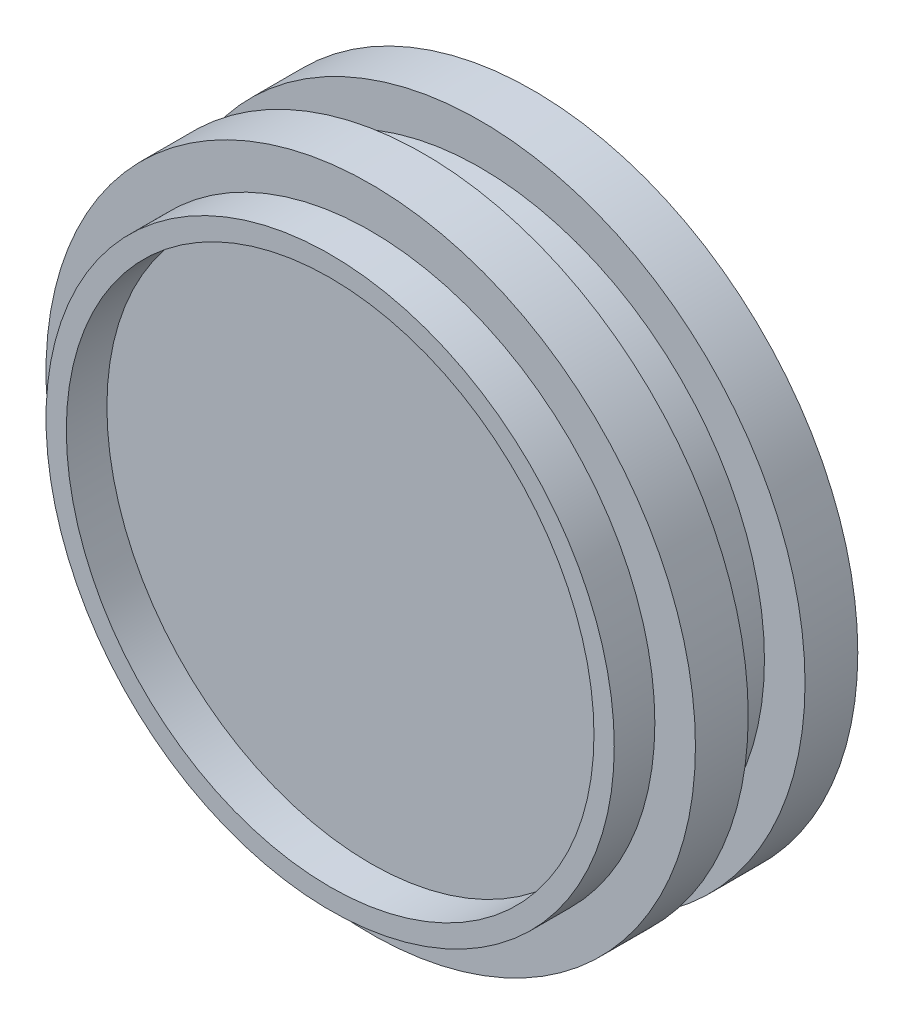
SolidWorks part; units mm, degrees
ref_plane "Front Plane" through (0, 0, 0) normal (0, 0, 1) x (1, 0, 0)
ref_plane "Top Plane" through (0, 0, 0) normal (0, 1, 0) x (1, 0, 0)
ref_plane "Right Plane" through (0, 0, 0) normal (1, 0, 0) x (0, 0, -1)
sketch "Sketch1" plane through (0, 0, 0) normal (0, 0, 1) x (1, 0, 0)
  circle A0 centre (0, 0) radius 82.55
  circle A1 centre (0, 0) radius 88.9
  circle A2 centre (0, 0) radius 101.6
  dimension "D1" = 165.1
  dimension "D2" = 177.8
  dimension "D3" = 203.2
extrude "Boss-Extrude1" add sketch "Sketch1" along normal blind 12.7 and the other way blind 50.8 contours A1 A0 region at (-86.3855, 0, 0)
extrude "Boss-Extrude2" add sketch "Sketch1<3>" against normal blind 50.8 separate body contours A2 A1 region at (-98.7263, 0, 0)
sketch "Sketch1<3>" plane through (0, 0, 0) normal (0, 0, 1) x (1, 0, 0) same geometry as "Sketch1"
extrude "Boss-Extrude3" add sketch "Sketch1<4>" against normal blind 25.4 separate body contours A0 region at (0, 0, 0)
sketch "Sketch1<4>" plane through (0, 0, 0) normal (0, 0, 1) x (1, 0, 0) same geometry as "Sketch1"
sketch "Sketch4" plane through (0, 0, 0) normal (0, 1, 0) x (1, 0, 0)
  line L0 (101.6, 25.4) -> (-112.628, 25.4) construction
  line L1 (101.6, 0) -> (101.6, 50.8) construction
  line L2 (101.6, 34.29) -> (88.9, 34.29)
  line L3 (88.9, 34.29) -> (88.9, 16.51)
  line L4 (88.9, 16.51) -> (101.6, 16.51)
  line L5 (101.6, 16.51) -> (101.6, 34.29)
  line L7 (0, 0) -> (0, -160.0116) construction
  dimension "D1" = 17.78
  dimension "D3" = 12.7
revolve "Cut-Revolve1" cut sketch "Sketch4" angle 360 about L7
